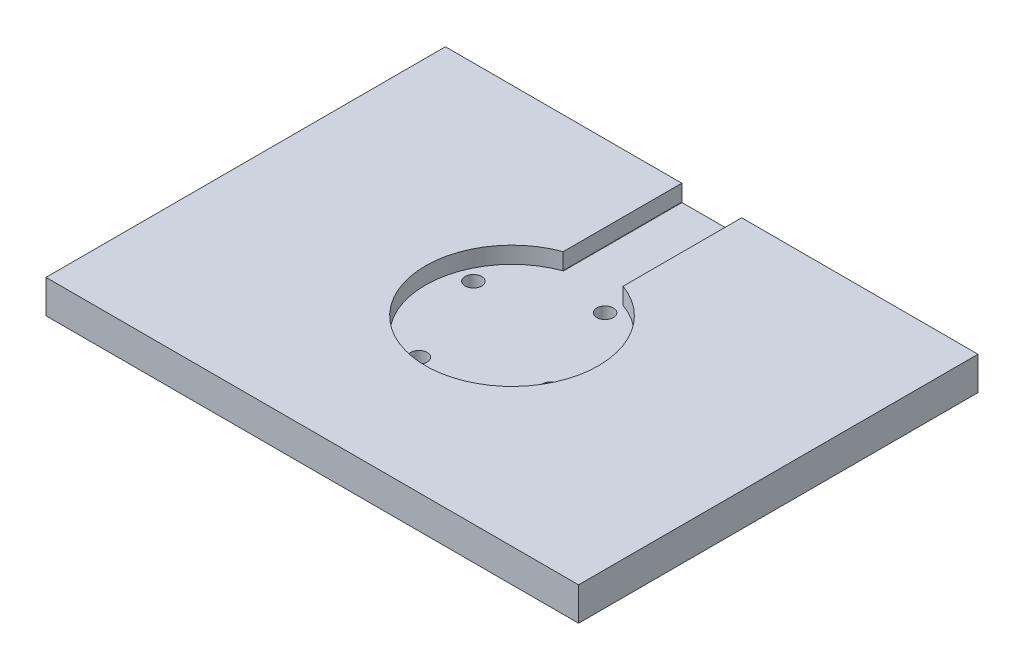
SolidWorks part; units mm, degrees
material "6061-T4 (SS)"
ref_plane "Front Plane" through (0, 0, 0) normal (0, 0, 1) x (1, 0, 0)
ref_plane "Top Plane" through (0, 0, 0) normal (0, 1, 0) x (1, 0, 0)
ref_plane "Right Plane" through (0, 0, 0) normal (1, 0, 0) x (0, 0, -1)
sketch "Sketch1" plane through (0, 0, 0) normal (0, 1, 0) x (1, 0, 0)
  line L1 (80, 60) -> (-80, 60)
  line L2 (80, 60) -> (80, -60)
  line L3 (80, -60) -> (-80, -60)
  line L4 (-80, 60) -> (-80, -60)
  line L5 (80, 60) -> (-80, -60) construction
  line L6 (80, -60) -> (-80, 60) construction
  point P0 (0, 0)
  dimension "D1" = 120
  dimension "D2" = 160
extrude "base" add sketch "Sketch1" along normal blind 10
sketch "Sketch2" plane through (0, 10, 0) normal (0, 1, 0) x (1, 0, 0)
  circle A0 centre (0, 0) radius 26
  dimension "D1" = 52
extrude "load cell cut" cut sketch "Sketch2" against normal blind 5 contours A0
sketch "post positioning points" plane through (0, 10, 0) normal (0, 1, 0) x (1, 0, 0)
  line L0 (-80, 60) -> (-80, -60) construction
  line L1 (-80, -60) -> (80, -60) construction
  line L2 (80, -60) -> (80, 60) construction
  line L3 (80, 60) -> (-80, 60) construction
  point P0 (-65, -45)
  point P5 (-5, 45)
  point P6 (-65, 45)
  point P7 (65, 45)
  point P8 (65, -45)
  point P9 (20, -45)
  point P10 (8.4315, 65)
  dimension "D1" = 15
  dimension "D2" = 15
  dimension "D3" = 15
  dimension "D4" = 15
  dimension "D5" = 85
  dimension "D7" = 60
  dimension "D6" = 60
sketch "Sketch6" plane through (0, 0, -60) normal (0, 0, 1) x (1, 0, 0)
  line L0 (-80, 0) -> (80, 0) construction
  line L1 (9, 10) -> (-9, 10)
  line L2 (9, 10) -> (9, 5)
  line L3 (9, 5) -> (-9, 5)
  line L4 (-9, 10) -> (-9, 5)
  line L5 (9, 10) -> (-9, 5) construction
  line L6 (9, 5) -> (-9, 10) construction
  line L7 (-80, 10) -> (80, 10) construction
  point P0 (0, 7.5)
  point P8 (0, 0)
  dimension "D1" = 18
  dimension "D2" = 5
extrude "cut wire" cut sketch "Sketch6" along normal up to next contours L4 L3 L2 L1
sketch "Sketch7" plane through (0, 0, -60) normal (0, 0, 1) x (1, 0, 0)
  line L1 (5, 10) -> (-5, 10)
  line L2 (5, 10) -> (5, 0)
  line L3 (5, 0) -> (-5, 0)
  line L4 (-5, 10) -> (-5, 0)
  line L5 (5, 10) -> (-5, 0) construction
  line L6 (5, 0) -> (-5, 10) construction
  line L7 (-80, 0) -> (80, 0) construction
  line L8 (-80, 10) -> (80, 10) construction
  point P0 (0, 5)
  point P8 (0, 0)
  dimension "D1" = 10
  dimension "D2" = 10
extrude "cut wire 2" [suppressed] cut sketch "Sketch7" along normal up to next
fillet "Fillet5" [suppressed] radius 10
fillet "Fillet6" radius 0.1 2 edges at (9, 5, -42.1963) (-9, 5, -42.1963)
fillet "Fillet7" [suppressed] radius 5
sketch "Sketch12" plane through (0, 0, 0) normal (0, -1, 0) x (1, 0, 0)
  line L0 (0, 0) -> (80, 0) construction
  line L1 (19.771, 8.1894) -> (-8.1894, 19.771) construction
  line L2 (-8.1894, 19.771) -> (-19.771, -8.1894) construction
  line L3 (-19.771, -8.1894) -> (8.1894, -19.771) construction
  line L4 (8.1894, -19.771) -> (19.771, 8.1894) construction
  line L5 (80, 60) -> (80, -60) construction
  circle A0 centre (0, 0) radius 15.1321 construction
  dimension "D1" = 22.5
  dimension "D2" = 21.4
hole_wizard "Ø5.0mm Dowel Hole1" positions "3DSketch4" profile "Sketch13" hole size "Ø5.0" standard "ANSI Metric" end condition up to next
sketch3d "3DSketch4"
  point P0 (-8.1894, 0, 19.771)
  point P3 (19.771, 0, 8.1894)
  point P6 (8.1894, 0, -19.771)
  point P9 (-19.771, 0, -8.1894)
sketch "Sketch13" plane through (-8.1894, 0, 19.771) normal (1, 0, 0) x (0, 0, -1)
  line L0 (0, 0) -> (0, 5)
  line L1 (0, 5) -> (2.5, 5)
  line L2 (2.5, 5) -> (2.5, 0)
  line L5 (2.5, 0) -> (0, 0)
  line L11 (0, -6.35) -> (0, 107.95) construction
  dimension "Thru Hole Dia." = 5
  dimension "Thru Hole Depth" = 5
fillet "Fillet8" [suppressed] radius 5
equation "\"D2@post positioning points\" = \"D1@post positioning points\""
equation "\"D3@post positioning points\" = \"D1@post positioning points\""
equation "\"D4@post positioning points\" = \"D1@post positioning points\""
equation "\"D1@base\"=10"
equation "\"D1@load cell cut\"=5"
equation "\"D2@Sketch6\"=5"
